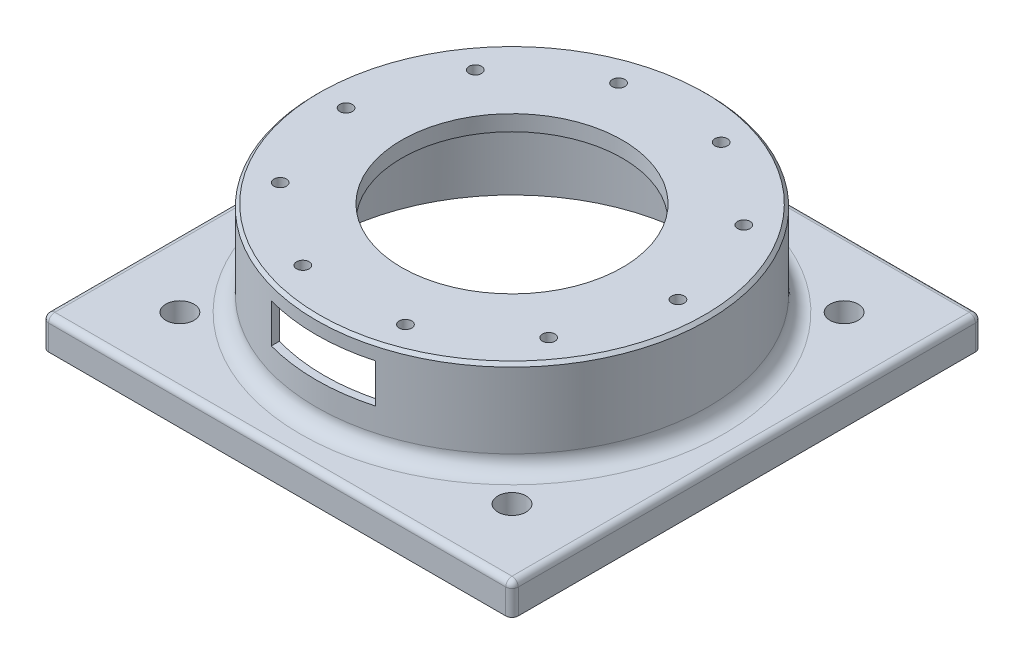
SolidWorks part; units mm, degrees
ref_plane "Спереди" through (0, 0, 0) normal (0, 0, 1) x (1, 0, 0)
ref_plane "Сверху" through (0, 0, 0) normal (0, 1, 0) x (1, 0, 0)
ref_plane "Справа" through (0, 0, 0) normal (1, 0, 0) x (0, 0, -1)
sketch "Эскиз1" plane through (0, 0, 0) normal (0, 1, 0) x (1, 0, 0)
  line L0 (0, 0) -> (53.033, 53.033) construction
  line L5 (75, -75) -> (-75, -75)
  line L6 (75, -75) -> (75, 75)
  line L7 (75, 75) -> (-75, 75)
  line L8 (-75, -75) -> (-75, 75)
  line L9 (75, -75) -> (-75, 75) construction
  line L10 (75, 75) -> (-75, -75) construction
  circle A2 centre (0, 0) radius 75 construction
  circle A3 centre (53.033, 53.033) radius 4.5
  circle A4 centre (0, 0) radius 75 construction
  circle A5 centre (53.033, -53.033) radius 4.5
  circle A6 centre (0, 0) radius 75 construction
  circle A7 centre (-53.033, -53.033) radius 4.5
  circle A8 centre (0, 0) radius 75 construction
  circle A9 centre (-53.033, 53.033) radius 4.5
  point P0 (0, 0)
  dimension "D3" = 150
  dimension "D4" = 9
  dimension "D1" = 150
  dimension "D2" = 150
  dimension "D5" = 4
extrude "Бобышка-Вытянуть1" add sketch "Эскиз1" along normal blind 10
fillet "Скругление1" radius 2 4 edges at (-75, 5, -75) (75, 5, -75) (-75, 5, 75) (75, 5, 75)
fillet "Скругление2" radius 2 8 edges at (-74.4142, 10, -74.4142) (74.4142, 10, -74.4142) (74.4142, 10, 74.4142) (-74.4142, 10, 74.4142) (0, 10, 75) (75, 10, 0) (0, 10, -75) (-75, 10, 0)
sketch "Эскиз4" plane through (0, 10, 0) normal (0, 1, 0) x (1, 0, 0)
  circle A0 centre (0, 0) radius 62.5
  dimension "D1" = 125
extrude "Бобышка-Вытянуть4" add sketch "Эскиз4" along normal blind 30 contours A0
fillet "Скругление5" radius 5 1 edges at (0, 10, 62.5)
sketch "Эскиз10" plane through (0, 0, 0) normal (0, -1, 0) x (1, 0, 0)
  circle A0 centre (0, 0) radius 60
  dimension "D1" = 120
sketch "Эскиз3" plane through (0, 10, 0) normal (0, 1, 0) x (1, 0, 0)
  line L0 (0, -75) -> (0, 75)
  line L1 (-73, 75) -> (73, 75) construction
  circle A1 centre (-53.033, 53.033) radius 6.25
  circle A2 centre (-53.033, -53.033) radius 6.25
  circle A3 centre (53.033, -53.033) radius 6.25
  circle A4 centre (53.033, 53.033) radius 6.25
  point P14 (0, 0)
  dimension "D2" = 12.5
  dimension "D3" = 12.5
  dimension "D1" = 150
extrude "Вырез-Вытянуть1" [suppressed] cut sketch "Эскиз3" along normal up to next contours A3 | A2 | A1 | A4
sketch "Эскиз11" plane through (0, 40, 0) normal (0, 1, 0) x (1, 0, 0)
  circle A0 centre (0, 0) radius 35.25
  dimension "D1" = 70.5
extrude "Вырез-Вытянуть2" cut sketch "Эскиз11" against normal through all contours A0
extrude "Вырез-Вытянуть3" cut sketch "Эскиз10" against normal blind 35 contours A0
sketch "Эскиз12" plane through (0, 40, 0) normal (0, 1, 0) x (1, 0, 0)
  line L0 (0, 0) -> (-53, 0) construction
  circle A0 centre (0, 0) radius 53 construction
  circle A1 centre (-53, 0) radius 2
  circle A2 centre (0, 0) radius 53
  circle A3 centre (0, 0) radius 35.25 construction
  circle A4 centre (-42.8779, 31.1526) radius 2
  circle A5 centre (0, 0) radius 53
  circle A6 centre (-16.3779, 50.406) radius 2
  circle A7 centre (0, 0) radius 53
  circle A8 centre (16.3779, 50.406) radius 2
  circle A9 centre (0, 0) radius 53
  circle A10 centre (42.8779, 31.1526) radius 2
  circle A11 centre (0, 0) radius 53
  circle A12 centre (53, 0) radius 2
  circle A13 centre (0, 0) radius 53
  circle A14 centre (42.8779, -31.1526) radius 2
  circle A15 centre (0, 0) radius 53
  circle A16 centre (16.3779, -50.406) radius 2
  circle A17 centre (0, 0) radius 53
  circle A18 centre (-16.3779, -50.406) radius 2
  circle A19 centre (0, 0) radius 53
  circle A20 centre (-42.8779, -31.1526) radius 2
  dimension "D2" = 4
  dimension "D3" = 53
  dimension "D5" = 53
  dimension "D4" = 10
extrude "Вырез-Вытянуть4" cut sketch "Эскиз12" against normal through all contours A4 | A1 | A20 | A18 | A16 | A14 | A12 | A10 | A8 | A6
chamfer "Фаска2" distance 1 angle 45 1 edges at (0, 40, 62.5)
ref_plane "Смещенная плоскость для разъема" through (0, 0, 62.5) normal (0, 0, 1) x (1, 0, 0)
sketch "Эскиз14" plane through (0, 0, 62.5) normal (0, 0, 1) x (1, 0, 0)
  line L0 (61.5, 40) -> (-61.5, 40) construction
  line L1 (16.625, 22.5) -> (-16.625, 22.5)
  line L2 (16.625, 22.5) -> (16.625, 35)
  line L3 (16.625, 35) -> (-16.625, 35)
  line L4 (-16.625, 22.5) -> (-16.625, 35)
  line L5 (16.625, 22.5) -> (-16.625, 35) construction
  line L6 (16.625, 35) -> (-16.625, 22.5) construction
  line L7 (-62.5, 39) -> (-62.5, 15) construction
  point P0 (0, 28.75)
  dimension "D1" = 33.25
  dimension "D2" = 12.5
  dimension "D3" = 5
  dimension "D4" = 45.875
extrude "Вырез-Вытянуть5" cut sketch "Эскиз14" against normal blind 5
equation "\"D2@Эскиз1\"=\"D1@Эскиз1\""
equation "\"D3@Эскиз1\"=\"D1@Эскиз1\""
equation "\"D3@Эскиз3\"=\"D2@Эскиз3\""
